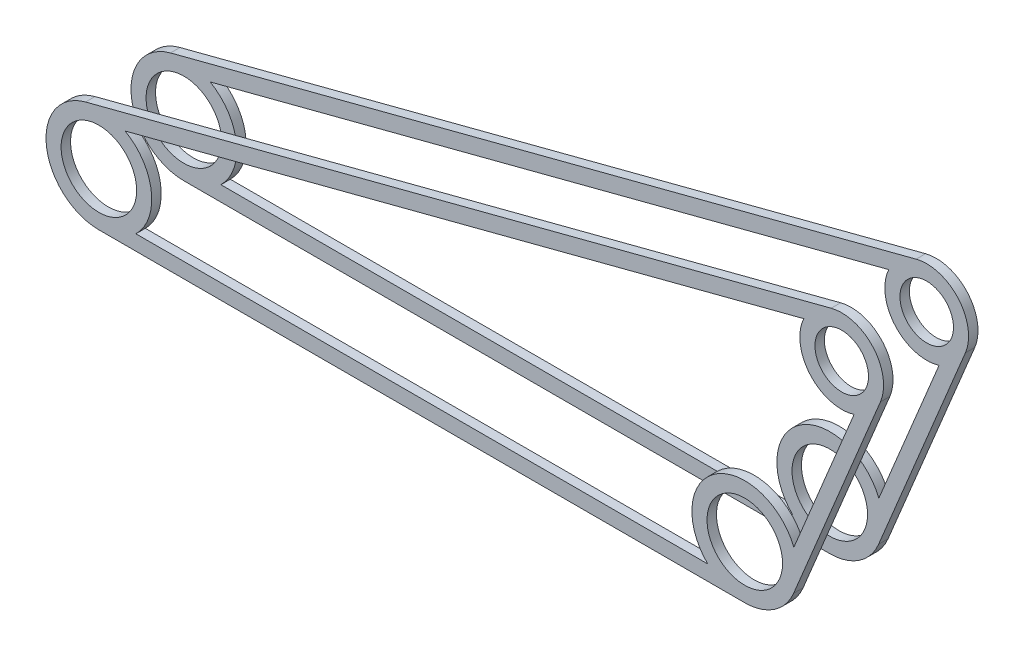
SolidWorks part; units mm, degrees
material "AISI 4130 Steel, annealed at 865C"
ref_plane "Front Plane" through (0, 0, 0) normal (0, 0, 1) x (1, 0, 0)
ref_plane "Top Plane" through (0, 0, 0) normal (0, 1, 0) x (1, 0, 0)
ref_plane "Right Plane" through (0, 0, 0) normal (1, 0, 0) x (0, 0, -1)
sketch "Sketch1" plane through (0, 0, 0) normal (0, 0, 1) x (1, 0, 0)
  line L0 (0, 0) -> (108.585, 0) construction
  line L1 (108.585, 0) -> (124.8778, 34.4406) construction
  line L2 (124.8778, 34.4406) -> (0, 0) construction
  line L3 (-2.2409, 8.6029) -> (123.1032, 41.2533)
  line L4 (131.3803, 31.7426) -> (116.7963, -3.407)
  line L5 (108.585, -8.89) -> (0, -8.89)
  line L6 (-1.6007, 6.1449) -> (123.7434, 38.7953)
  line L7 (0, -6.35) -> (108.585, -6.35)
  line L8 (114.4502, -2.4335) -> (129.0342, 32.7161)
  line L9 (111.596, -21.6868) -> (108.585, 0) construction
  circle A0 centre (0, 0) radius 6.35
  circle A1 centre (108.585, 0) radius 6.35
  circle A2 centre (124.8778, 34.4406) radius 4.5
  circle A3 centre (0, 0) radius 8.89
  circle A4 centre (108.585, 0) radius 8.89
  circle A5 centre (124.8778, 34.4406) radius 7.04
  dimension "D1" = 9
  dimension "D2" = 12.7
  dimension "D3" = 12.7
  dimension "D6" = 2.54
  dimension "D7" = 2.54
  dimension "D8" = 2.54
  dimension "D4" = 108.585
  dimension "D5" = 129.54
  dimension "D9" = 38.1
extrude "Boss-Extrude1" add sketch "Sketch1" along normal blind 1.5875 from offset 6.35 contours A5 L3 A3 L6 | L6 A3 L7 A0 | A4 L7 A3 L5 | L7 A4 L8 A1 | A5 L8 A4 L4 | A5 L6 A2 L8 | L7 A3 L6 A0 | L8 A4 L7 A1 | L6 A5 L8 A2 region at (1.146, 8.5805, 0) region at (60.9965, 23.7793, 0) region at (129.0654, 39.8588, 0) region at (54.2925, -7.6406, 0) region at (7.54, 4.3695, 0) region at (121.1641, 37.9583, 0) region at (105.2983, -8.0507, 0) region at (123.0705, 14.8619, 0) region at (103.7755, 7.2025, 0)
extrude "Boss-Extrude2" add sketch "Sketch1<4>" against normal blind 1.5875 from offset 6.35 separate body contours A5 L3 A3 L6 | L6 A3 L7 A0 | L7 A3 L6 A0 | A4 L7 A3 L5 | L7 A4 L8 A1 | L8 A4 L7 A1 | A5 L8 A4 L4 | L6 A5 L8 A2 | A5 L6 A2 L8 region at (1.146, 8.5805, 0) region at (60.9965, 23.7793, 0) region at (129.0654, 39.8588, 0) region at (54.2925, -7.6406, 0) region at (7.54, 4.3695, 0) region at (121.1641, 37.9583, 0) region at (105.2983, -8.0507, 0) region at (123.0705, 14.8619, 0) region at (103.7755, 7.2025, 0) offset against normal yes
sketch "Sketch1<4>" plane through (0, 0, 0) normal (0, 0, 1) x (1, 0, 0) same geometry as "Sketch1"
equation "\"D19@Boss-Extrude2\"=.45"
